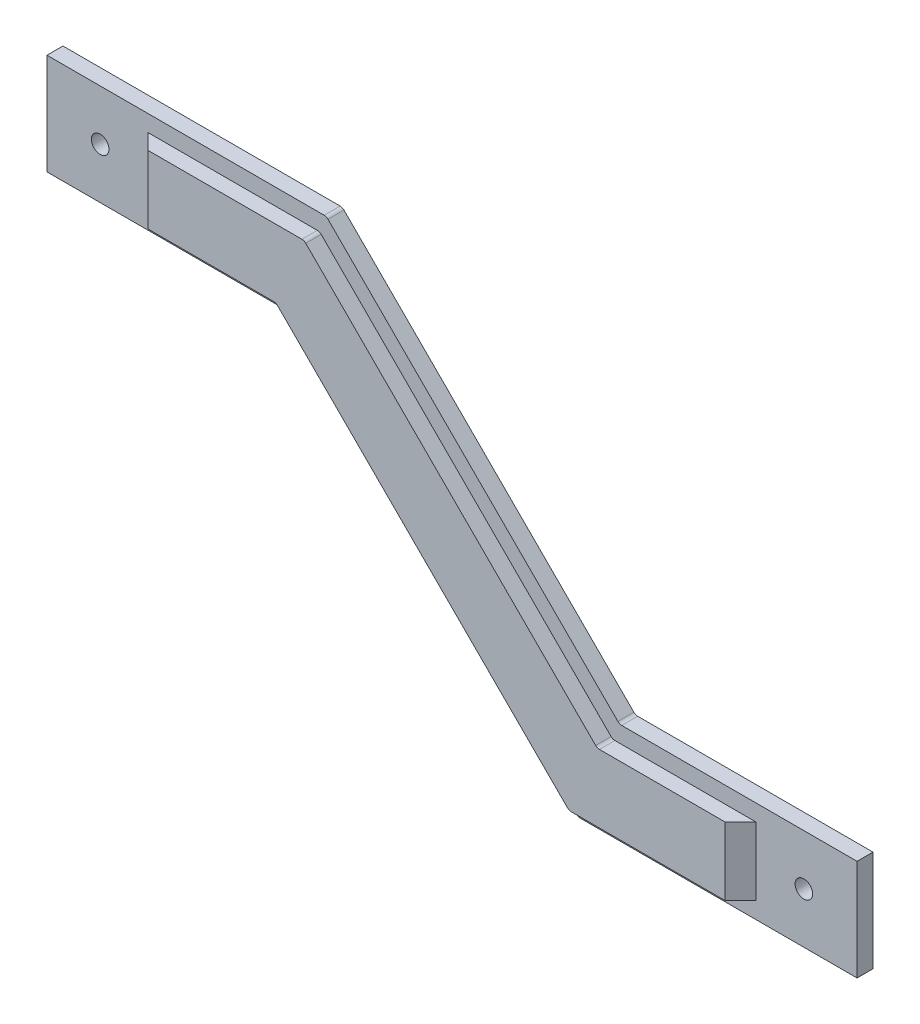
SolidWorks part; units mm, degrees
ref_plane "前视基准面" through (0, 0, 0) normal (0, 0, 1) x (1, 0, 0)
ref_plane "上视基准面" through (0, 0, 0) normal (0, 1, 0) x (1, 0, 0)
ref_plane "右视基准面" through (0, 0, 0) normal (1, 0, 0) x (0, 0, -1)
sketch "草图1" plane through (0, 0, 0) normal (0, 0, 1) x (1, 0, 0)
  line L0 (-76.15, 37.05) -> (-23.615, 37.05)
  line L1 (-23.615, 37.05) -> (31.485, -18.05)
  line L2 (31.485, -18.05) -> (76.15, -18.05)
  line L3 (76.15, -18.05) -> (76.15, -37.05)
  line L4 (76.15, -37.05) -> (23.615, -37.05)
  line L5 (23.615, -37.05) -> (-31.485, 18.05)
  line L6 (-31.485, 18.05) -> (-76.15, 18.05)
  line L7 (-76.15, 18.05) -> (-76.15, 37.05)
  line L8 (-23.615, 37.05) -> (23.615, -37.05) construction
  line L9 (-31.485, 18.05) -> (31.485, -18.05) construction
  circle A0 centre (-66.15, 27.55) radius 1.65
  circle A1 centre (66.15, -27.55) radius 1.65
  dimension "D2" = 3.3
  dimension "D1" = 19
  dimension "D3" = 132.3
  dimension "D4" = 55.1
  dimension "D5" = 9.5
  dimension "D6" = 9.5
  dimension "D7" = 135
  dimension "D8" = 19
  dimension "D9" = 10
  dimension "D10" = 10
extrude "凸台-拉伸1" add sketch "草图1" along normal blind 3
sketch "草图2" plane through (0, 0, 3) normal (0, 0, 1) x (1, 0, 0)
  line L0 (-57.15, 33.95) -> (-57.15, 21.15)
  line L1 (-57.15, 21.15) -> (-30.201, 21.15)
  line L2 (-30.201, 21.15) -> (24.899, -33.95)
  line L3 (24.899, -33.95) -> (57.15, -33.95)
  line L4 (57.15, -33.95) -> (57.15, -21.15)
  line L5 (57.15, -21.15) -> (30.201, -21.15)
  line L6 (30.201, -21.15) -> (-24.899, 33.95)
  line L7 (-24.899, 33.95) -> (-57.15, 33.95)
  line L8 (-23.615, 37.05) -> (-76.15, 37.05) construction
  line L9 (23.615, -37.05) -> (76.15, -37.05) construction
  line L10 (76.15, -37.05) -> (76.15, -18.05) construction
  line L11 (-76.15, 37.05) -> (-76.15, 18.05) construction
  line L12 (31.485, -18.05) -> (-23.615, 37.05) construction
  dimension "D1" = 12.8
  dimension "D2" = 12.8
  dimension "D3" = 3.1
  dimension "D4" = 3.1
  dimension "D5" = 19
  dimension "D6" = 19
  dimension "D7" = 12.8
extrude "凸台-拉伸2" add sketch "草图2" along normal blind 2.9
chamfer "倒角1" distance 2.9 angle 45 2 edges at (57.15, -27.55, 5.9) (-57.15, 27.55, 5.9)
fillet "圆角1" radius 1 8 edges at (-24.899, 33.95, 4.45) (-23.615, 37.05, 1.5) (31.485, -18.05, 1.5) (30.201, -21.15, 4.45) (23.615, -37.05, 1.5) (24.899, -33.95, 4.45) (-31.485, 18.05, 1.5) (-30.201, 21.15, 4.45)
